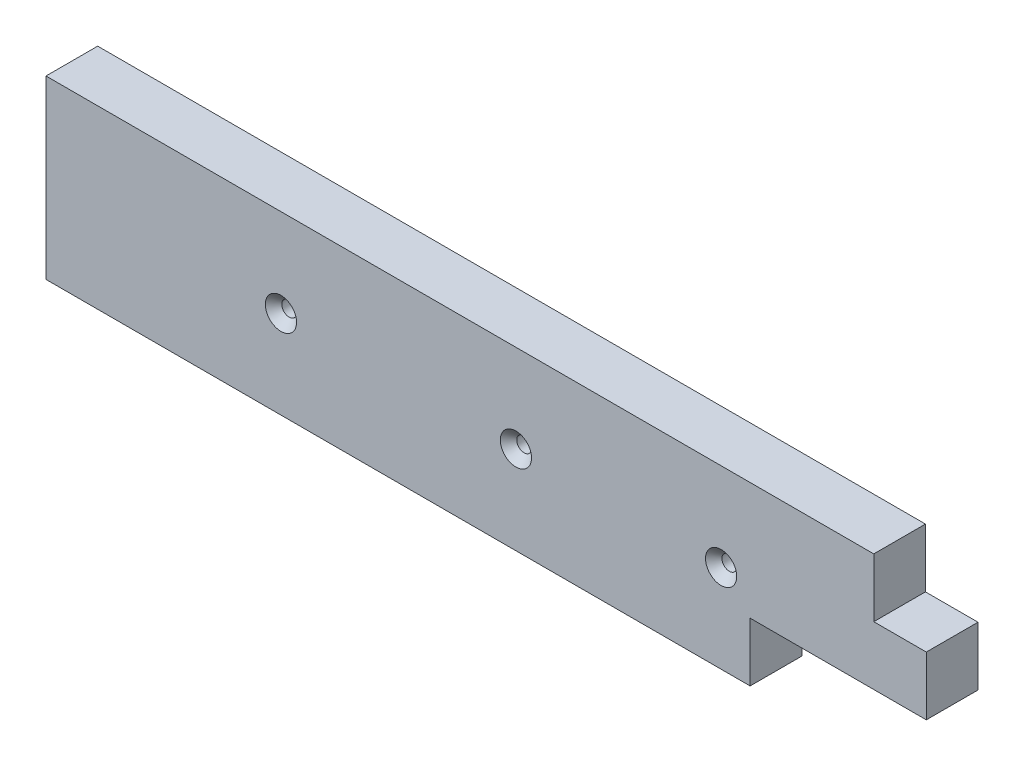
SolidWorks part; units mm, degrees
ref_plane "Front Plane" through (0, 0, 0) normal (0, 0, 1) x (1, 0, 0)
ref_plane "Top Plane" through (0, 0, 0) normal (0, 1, 0) x (1, 0, 0)
ref_plane "Right Plane" through (0, 0, 0) normal (1, 0, 0) x (0, 0, -1)
sketch "Sketch1" plane through (0, 0, 0) normal (0, 1, 0) x (1, 0, 0)
  line L1 (-190.3259, -11.176) -> (190.3259, -11.176)
  line L2 (-190.3259, -11.176) -> (-190.3259, 11.176)
  line L3 (-190.3259, 11.176) -> (190.3259, 11.176)
  line L4 (190.3259, -11.176) -> (190.3259, 11.176)
  line L5 (-190.3259, -11.176) -> (190.3259, 11.176) construction
  line L6 (-190.3259, 11.176) -> (190.3259, -11.176) construction
  point P0 (0, 0)
extrude "Boss-Extrude1" add sketch "Sketch1" along normal mid plane 76.2 contours L1 L4 L3 L2
sketch "Sketch3" plane through (0, 0, 11.176) normal (0, 0, 1) x (1, 0, 0)
  line L1 (167.6064, 12.7) -> (190.3259, 12.7)
  line L2 (190.3259, 38.1) -> (190.3259, 12.7)
  line L3 (167.6064, 12.7) -> (167.6064, 38.1)
  line L4 (167.6064, 38.1) -> (190.3259, 38.1)
  line L5 (114.1394, -12.7) -> (190.3259, -12.7)
  line L6 (114.1394, -12.7) -> (114.1394, -38.1)
  line L7 (114.1394, -38.1) -> (190.3259, -38.1)
  line L8 (190.3259, -12.7) -> (190.3259, -38.1)
hole_wizard "CSK for M6 Hex Socket Countersunk Head Screw6" positions "Sketch21" profile "Sketch20" countersink size "M6" standard "Lanco STD" end condition through all
sketch "Sketch21" plane through (0, 0, 11.176) normal (0, 0, 1) x (1, 0, 0)
  line L0 (-190.3259, 38.1) -> (-190.3259, -38.1) construction
  point P0 (-88.7259, 0)
  point P3 (-190.3259, 0)
  dimension "D1" = 101.6
sketch "Sketch20" plane through (-88.7259, 0, 11.176) normal (1, 0, 0) x (0, -1, 0)
  line L0 (0, 0) -> (0, 22.352)
  line L1 (0, 22.352) -> (3.2, 22.352)
  line L2 (3.2, 22.352) -> (3.2, 3.55)
  line L3 (3.2, 3.55) -> (6.75, 0)
  line L5 (6.75, 0) -> (0, 0)
  line L6 (-3.2, 3.55) -> (-6.75, 0) construction
  line L11 (0, -6.35) -> (0, 107.95) construction
  dimension "Thru Hole Dia." = 6.4
  dimension "Thru Hole Depth" = 22.352
  dimension "Near C'Sink Dia." = 13.5
  dimension "Near C'Sink Angle" = 90
hole_wizard "CSK for M6 Hex Socket Countersunk Head Screw7" positions "Sketch23" profile "Sketch22" countersink size "M6" standard "Lanco STD" end condition through all
sketch "Sketch23" plane through (0, 0, 11.176) normal (0, 0, 1) x (1, 0, 0)
  line L1 (-190.3259, 38.1) -> (-190.3259, -38.1) construction
  point P0 (12.8741, 0)
  point P5 (-190.3259, 0)
  dimension "D1" = 203.2
sketch "Sketch22" plane through (12.8741, 0, 11.176) normal (1, 0, 0) x (0, -1, 0)
  line L0 (0, 0) -> (0, 22.352)
  line L1 (0, 22.352) -> (3.2, 22.352)
  line L2 (3.2, 22.352) -> (3.2, 3.55)
  line L3 (3.2, 3.55) -> (6.75, 0)
  line L5 (6.75, 0) -> (0, 0)
  line L6 (-3.2, 3.55) -> (-6.75, 0) construction
  line L11 (0, -6.35) -> (0, 107.95) construction
  dimension "Thru Hole Dia." = 6.4
  dimension "Thru Hole Depth" = 22.352
  dimension "Near C'Sink Dia." = 13.5
  dimension "Near C'Sink Angle" = 90
hole_wizard "CSK for M6 Hex Socket Countersunk Head Screw8" positions "Sketch25" profile "Sketch24" countersink size "M6" standard "Lanco STD" end condition through all
sketch "Sketch25" plane through (0, 0, 11.176) normal (0, 0, 1) x (1, 0, 0)
  point P0 (101.6, 0)
  dimension "D1" = 101.6
sketch "Sketch24" plane through (101.6, 0, 11.176) normal (1, 0, 0) x (0, -1, 0)
  line L0 (0, 0) -> (0, 22.352)
  line L1 (0, 22.352) -> (3.2, 22.352)
  line L2 (3.2, 22.352) -> (3.2, 3.55)
  line L3 (3.2, 3.55) -> (6.75, 0)
  line L5 (6.75, 0) -> (0, 0)
  line L6 (-3.2, 3.55) -> (-6.75, 0) construction
  line L11 (0, -6.35) -> (0, 107.95) construction
  dimension "Thru Hole Dia." = 6.4
  dimension "Thru Hole Depth" = 22.352
  dimension "Near C'Sink Dia." = 13.5
  dimension "Near C'Sink Angle" = 90
extrude "Cut-Extrude1" cut sketch "Sketch3" against normal through all
